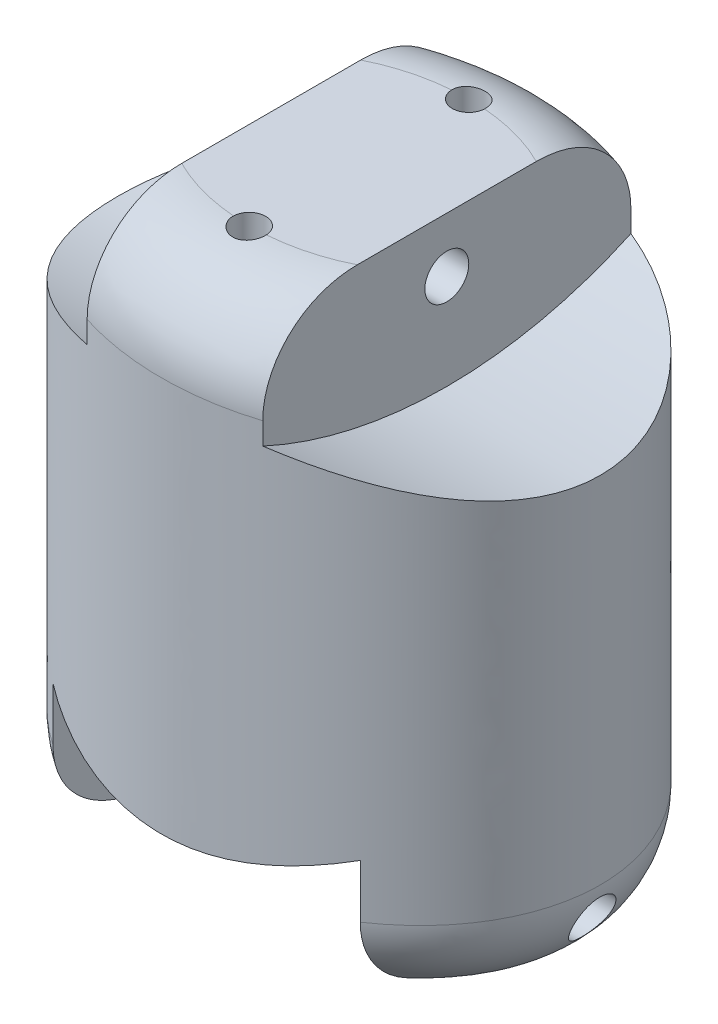
SolidWorks part; units mm, degrees
ref_plane "Front Plane" through (0, 0, 0) normal (0, 0, 1) x (1, 0, 0)
ref_plane "Top Plane" through (0, 0, 0) normal (0, 1, 0) x (1, 0, 0)
ref_plane "Right Plane" through (0, 0, 0) normal (1, 0, 0) x (0, 0, -1)
sketch "Sketch1" plane through (0, 0, 0) normal (0, 1, 0) x (1, 0, 0)
  line L0 (-13.97, 0) -> (13.97, 0) construction
  line L1 (0, -11.43) -> (0, 11.43) construction
  ellipse E0 centre (0, 0) end of major axis (13.97, 0) minor radius 11.43
  dimension "D1" = 27.94
  dimension "D2" = 22.86
extrude "Boss-Extrude1" add sketch "Sketch1" along normal blind 34.29
fillet "Fillet1" radius 5.08 2 edges at (13.97, 0, 0) (13.97, 34.29, 0)
sketch "Sketch2" plane through (0, 0, 0) normal (0, 0, 1) x (1, 0, 0)
  line L1 (-8.89, 0) -> (8.89, 0)
  line L2 (-8.89, 0) -> (-8.89, 6.35)
  line L3 (-8.89, 6.35) -> (8.89, 6.35)
  line L4 (8.89, 0) -> (8.89, 6.35)
  dimension "D1" = 17.78
  dimension "D2" = 6.35
extrude "Cut-Extrude1" cut sketch "Sketch2" against normal through all both and the other way through all
sketch "Sketch3" plane through (-8.89, 0, 0) normal (1, 0, 0) x (0, 0, -1)
  line L0 (0, 0) -> (0, 6.35) construction
  line L2 (8.817, 6.35) -> (-8.817, 6.35) construction
  circle A0 centre (0, 3.175) radius 1.27
  dimension "D2" = 2.54
  dimension "D1" = 6.35
extrude "Cut-Extrude2" cut sketch "Sketch3" against normal through all both and the other way through all
sketch "Sketch4" plane through (0, 6.35, 0) normal (0, -1, 0) x (-1, 0, 0)
  line L0 (0, -11.43) -> (0, 11.43) construction
  circle A0 centre (0, -6.35) radius 0.9525
  circle A1 centre (0, 6.35) radius 0.9525
  ellipse E2 centre (0, 0) end of major axis (-13.97, 0) minor radius 11.43 (-8.89, -8.817) -> (8.89, -8.817) ccw construction
  ellipse E3 centre (0, 0) end of major axis (-13.97, 0) minor radius 11.43 (8.89, 8.817) -> (-8.89, 8.817) ccw construction
  dimension "D2" = 1.905
  dimension "D3" = 6.35
  dimension "D4" = 1.905
  dimension "D5" = 6.35
  dimension "D1" = 22.86
extrude "Cut-Extrude3" cut sketch "Sketch4" against normal through all both and the other way through all
sketch "Sketch5" plane through (0, 0, 0) normal (0, 0, 1) x (1, 0, 0)
  line L1 (-8.89, 34.29) -> (8.89, 34.29)
  line L3 (-6.985, 27.94) -> (6.985, 27.94)
  line L5 (13.97, 5.08) -> (13.97, 29.21) construction
  line L6 (-13.97, 34.29) -> (13.97, 34.29)
  line L7 (-13.97, 34.29) -> (-13.97, 27.94)
  line L8 (-13.97, 27.94) -> (13.97, 27.94)
  line L9 (13.97, 34.29) -> (13.97, 27.94)
  line L10 (0, 34.29) -> (0, 27.94) construction
  line L11 (13.97, 31.115) -> (-13.97, 31.115) construction
  line L12 (13.97, 5.08) -> (13.97, 29.21) construction
  line L13 (-5.08, 27.94) -> (5.08, 27.94)
  line L14 (-5.08, 27.94) -> (-5.08, 34.29)
  line L15 (-5.08, 34.29) -> (5.08, 34.29)
  line L16 (5.08, 27.94) -> (5.08, 34.29)
  line L17 (-5.08, 27.94) -> (5.08, 34.29) construction
  line L18 (-5.08, 34.29) -> (5.08, 27.94) construction
  spline S0 degree 3 poles (-8.89, 34.29) (-11.8658, 34.29) (-13.97, 32.1858) (-13.97, 29.21) knots 0 0 0 0 1 1 1 1 weights 1 0.804738 0.804738 1 construction
  point P19 (0, 31.115)
  point P24 (3.1418, 22.225)
  dimension "D1" = 6.35
  dimension "D2" = 0
  dimension "D3" = 0
  dimension "D4" = 0
  dimension "D5" = 6.35
  dimension "D6" = 27.94
  dimension "D7" = 10.16
  dimension ".55" = 13.97
extrude "Cut-Extrude4" cut sketch "Sketch5" against normal through all both and the other way through all
sketch "Sketch6" plane through (6.985, 0, 0) normal (1, 0, 0) x (0, 0, -1)
  line L0 (0, 34.29) -> (0, 27.94) construction
  line L1 (5.1754, 34.29) -> (-5.1754, 34.29) construction
  circle A0 centre (0, 31.115) radius 1.27
  dimension "D2" = 2.54
  dimension "D1" = 6.35
  dimension "D3" = 0
extrude "Cut-Extrude5" cut sketch "Sketch6" against normal through all both and the other way through all
sketch "Sketch7" plane through (5.08, 0, 0) normal (1, 0, 0) x (0, 0, -1)
  line L0 (-10.6475, 27.94) -> (10.6475, 27.94)
  arc A0 (-10.6475, 27.94) -> (10.6475, 27.94) centre (0, 51.0006) ccw
  dimension "D2" = 25.4
  dimension "D1" = 21.295
extrude "Cut-Extrude6" cut sketch "Sketch7" along normal through all
sketch "Sketch8" plane through (-5.08, 0, 0) normal (-1, 0, 0) x (0, 0, 1)
  line L0 (-10.6475, 27.94) -> (10.6475, 27.94)
  arc A0 (-10.6475, 27.94) -> (10.6475, 27.94) centre (0, 51.0006) ccw
  dimension "D2" = 25.4
  dimension "D1" = 21.295
extrude "Cut-Extrude7" cut sketch "Sketch8" along normal through all
sketch "Sketch9" plane through (-8.89, 0, 0) normal (1, 0, 0) x (0, 0, -1)
  line L0 (-11.43, 6.35) -> (11.43, 6.35)
  arc A1 (-11.43, 6.35) -> (11.43, 6.35) centre (0, -7.2692) cw
  dimension "D2" = 17.78
  dimension "D1" = 22.86
extrude "Cut-Extrude8" cut sketch "Sketch9" along normal up to surface (17.78 mm away) up to face at (8.89, 3.175, -1.27)
